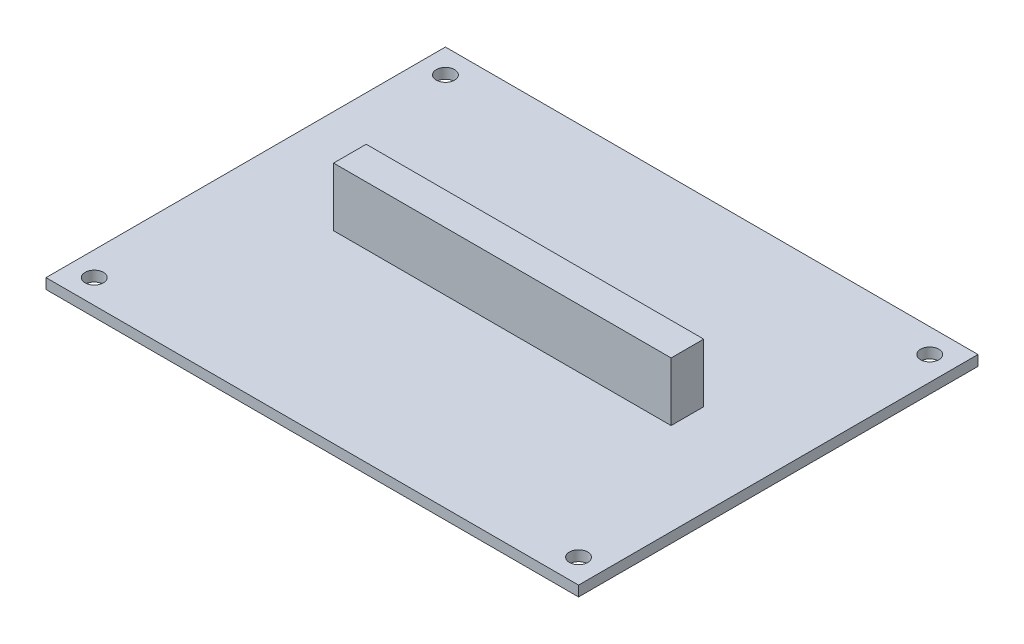
SolidWorks part; units mm, degrees
ref_plane "Front Plane" through (0, 0, 0) normal (0, 0, 1) x (1, 0, 0)
ref_plane "Top Plane" through (0, 0, 0) normal (0, 1, 0) x (1, 0, 0)
ref_plane "Right Plane" through (0, 0, 0) normal (1, 0, 0) x (0, 0, -1)
sketch "Sketch1" plane through (0, 0, 0) normal (0, 1, 0) x (1, 0, 0)
  line L0 (-36.375, 26.375) -> (-36.375, -26.375) construction
  line L1 (-40, -30) -> (40, -30)
  line L2 (-40, -30) -> (-40, 30)
  line L3 (-40, 30) -> (40, 30)
  line L4 (40, -30) -> (40, 30)
  line L5 (-40, -30) -> (40, 30) construction
  line L6 (-40, 30) -> (40, -30) construction
  line L7 (-36.375, 26.375) -> (36.375, 26.375) construction
  circle A4 centre (-36.375, 26.375) radius 1.375
  circle A5 centre (-36.375, -26.375) radius 1.375
  circle A6 centre (36.375, -26.375) radius 1.375
  circle A7 centre (36.375, 26.375) radius 1.375
  point P0 (0, 0)
  point P6 (0, 26.375)
  point P7 (-36.375, 0)
  dimension "D5" = 2.75
  dimension "D1" = 80
  dimension "D2" = 60
  dimension "D3" = 72.75
  dimension "D4" = 52.75
extrude "Boss-Extrude1" add sketch "Sketch1" along normal blind 1.55
sketch "Sketch2" plane through (0, 1.55, 0) normal (0, 1, 0) x (1, 0, 0)
  line L0 (-24.5, 2.6) -> (26.2, 2.6)
  line L1 (26.2, 2.6) -> (26.2, -2.3)
  line L2 (26.2, -2.3) -> (-24.5, -2.3)
  line L3 (-24.5, -2.3) -> (-24.5, 2.6)
  line L4 (40, 30) -> (-40, 30) construction
  line L5 (-40, -30) -> (40, -30) construction
  line L6 (40, -30) -> (40, 30) construction
  line L7 (-40, 30) -> (-40, -30) construction
  line L8 (0.85, 2.6) -> (0.85, -2.3) construction
  line L9 (0.85, 0.15) -> (-1.2594, 0.15) construction
  dimension "D1" = 32.3
  dimension "D2" = 32.6
  dimension "D3" = 64.5
  dimension "D4" = 66.2
extrude "Boss-Extrude2" add sketch "Sketch2" along normal blind 8.8
